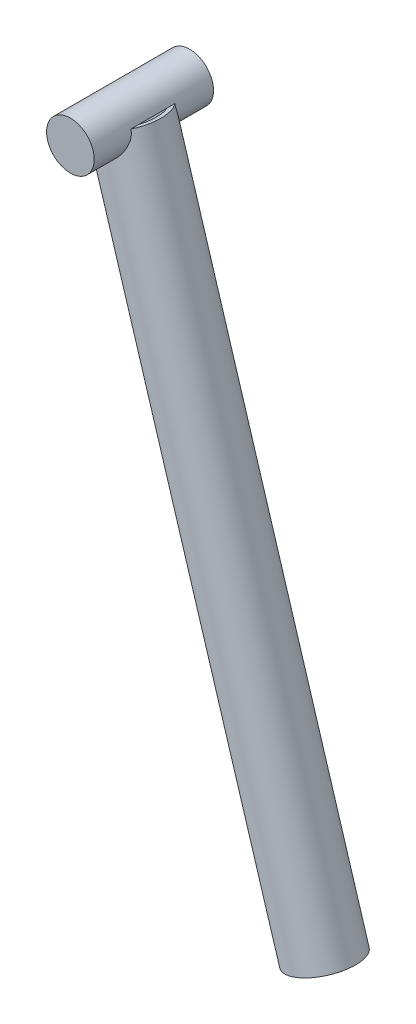
SolidWorks part; units mm, degrees
material "7075-T6 (SN)"
ref_plane "Alzado" through (0, 0, 0) normal (0, 0, 1) x (1, 0, 0)
ref_plane "Planta" through (0, 0, 0) normal (0, 1, 0) x (1, 0, 0)
ref_plane "Vista lateral" through (0, 0, 0) normal (1, 0, 0) x (0, 0, -1)
sketch3d "Sk_Tubo_tija"
  line L0 (-115.633, 378.2185, 0) -> (-197.1657, 644.9, 0)
  dimension "D1" = 278.8666
sweep "Tubo_tija" add path "Sk_Tubo_tija" circular profile diameter 27.2 parameters "D3"=27.2
sketch3d "Sk_Cabeza"
  line L0 (-197.1657, 644.9, -25) -> (-197.1657, 644.9, 25)
sweep "Cabeza" add path "Sk_Cabeza" circular profile diameter 20 parameters "D3"=20
sweep "Vaciado_Tubo_tija" cut path "Sk_Tubo_tija<2>" circular profile diameter 23.2 parameters "D3"=23.2
sketch3d "Sk_Tubo_tija<2>" same geometry as "Sk_Tubo_tija"
